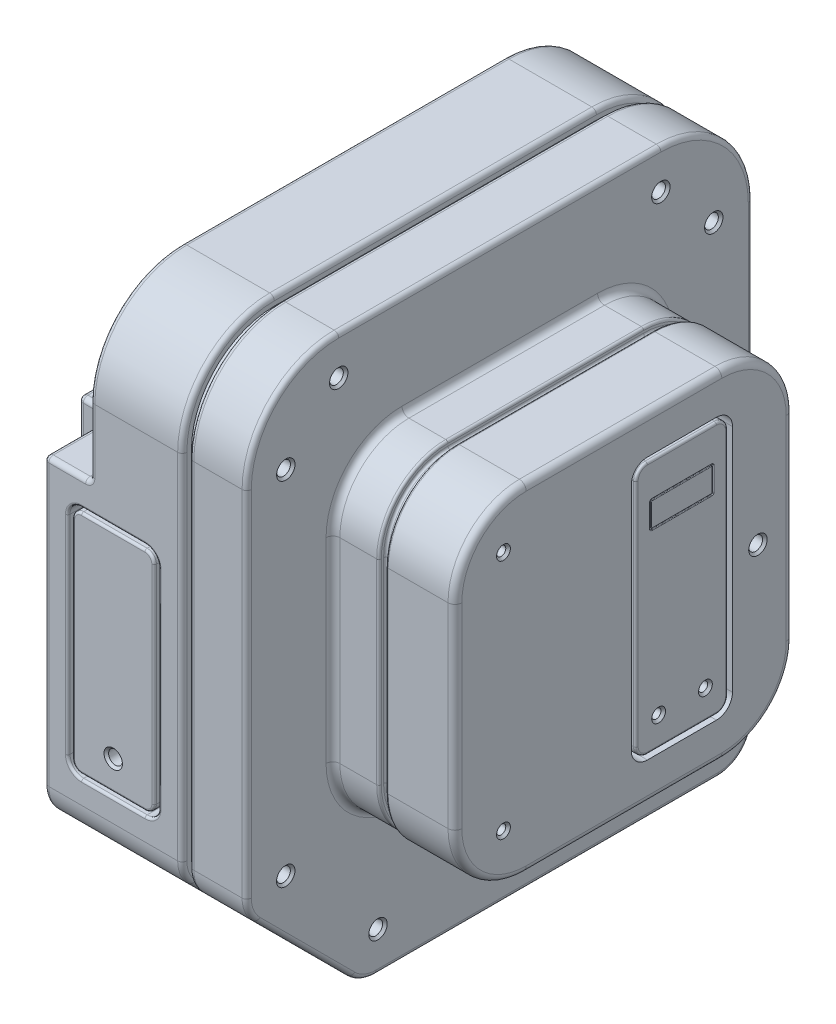
SolidWorks part; units mm, degrees
material "moto_black"
ref_plane "Front Plane" through (0, 0, 0) normal (0, 0, 1) x (1, 0, 0)
ref_plane "Top Plane" through (0, 0, 0) normal (0, 1, 0) x (1, 0, 0)
ref_plane "Right Plane" through (0, 0, 0) normal (1, 0, 0) x (0, 0, -1)
sketch "Sketch1" plane through (0, 0, 0) normal (1, 0, 0) x (0, 0, -1)
  line L0 (-105.6066, -79.3934) -> (-64.3934, -120.6066)
  line L1 (-70, 125) -> (70, 125)
  line L2 (-110, 85) -> (-110, -68.7868)
  line L3 (-53.7868, -125) -> (95, -125)
  line L4 (110, 85) -> (110, -110)
  line L5 (-110, 125) -> (110, -125) construction
  line L6 (-110, -125) -> (110, 125) construction
  arc A0 (70, 125) -> (110, 85) centre (70, 85) cw
  arc A1 (-70, 125) -> (-110, 85) centre (-70, 85) ccw
  arc A2 (95, -125) -> (110, -110) centre (95, -110) ccw
  arc A3 (-105.6066, -79.3934) -> (-110, -68.7868) centre (-95, -68.7868) cw
  arc A4 (-64.3934, -120.6066) -> (-53.7868, -125) centre (-53.7868, -110) ccw
  point P0 (0, 0)
  point P20 (-110, -75)
  point P23 (-60, -125)
  dimension "D3" = 40
  dimension "D4" = 15
  dimension "D5" = 15
  dimension "D1" = 250
  dimension "D2" = 220
extrude "Boss-Extrude1" add sketch "Sketch1" along normal blind 25
sketch "Sketch2" plane through (0, 0, 0) normal (-1, 0, 0) x (0, 0, 1)
  line L10 (-106, 85) -> (-106, -110)
  line L11 (-95, -121) -> (53.7868, -121)
  line L12 (61.565, -117.7782) -> (102.7782, -76.565)
  line L13 (106, -68.7868) -> (106, 85)
  line L14 (70, 121) -> (-70, 121)
  line L15 (-106, 85) -> (-106, -110)
  line L16 (-95, -121) -> (53.7868, -121)
  line L17 (61.565, -117.7782) -> (102.7782, -76.565)
  line L18 (106, -68.7868) -> (106, 85)
  line L19 (70, 121) -> (-70, 121)
  arc A10 (-70, 121) -> (-106, 85) centre (-70, 85) ccw
  arc A11 (-106, -110) -> (-95, -121) centre (-95, -110) ccw
  arc A12 (53.7868, -121) -> (61.565, -117.7782) centre (53.7868, -110) ccw
  arc A13 (102.7782, -76.565) -> (106, -68.7868) centre (95, -68.7868) ccw
  arc A14 (106, 85) -> (70, 121) centre (70, 85) ccw
  arc A15 (-70, 121) -> (-106, 85) centre (-70, 85) ccw
  arc A16 (-106, -110) -> (-95, -121) centre (-95, -110) ccw
  arc A17 (53.7868, -121) -> (61.565, -117.7782) centre (53.7868, -110) ccw
  arc A18 (102.7782, -76.565) -> (106, -68.7868) centre (95, -68.7868) ccw
  arc A19 (106, 85) -> (70, 121) centre (70, 85) ccw
  dimension "D1" = 4
extrude "Boss-Extrude2" add sketch "Sketch2" along normal blind 3
sketch "Sketch3" plane through (-3, 0, 0) normal (-1, 0, 0) x (0, 0, 1)
  line L10 (-110, 85) -> (-110, -110)
  line L11 (-95, -125) -> (53.7868, -125)
  line L12 (64.3934, -120.6066) -> (105.6066, -79.3934)
  line L13 (110, -68.7868) -> (110, 85)
  line L14 (70, 125) -> (-70, 125)
  line L15 (-110, 85) -> (-110, -110)
  line L16 (-95, -125) -> (53.7868, -125)
  line L17 (64.3934, -120.6066) -> (105.6066, -79.3934)
  line L18 (110, -68.7868) -> (110, 85)
  line L19 (70, 125) -> (-70, 125)
  arc A10 (-70, 125) -> (-110, 85) centre (-70, 85) ccw
  arc A11 (-110, -110) -> (-95, -125) centre (-95, -110) ccw
  arc A12 (53.7868, -125) -> (64.3934, -120.6066) centre (53.7868, -110) ccw
  arc A13 (105.6066, -79.3934) -> (110, -68.7868) centre (95, -68.7868) ccw
  arc A14 (110, 85) -> (70, 125) centre (70, 85) ccw
  arc A15 (-70, 125) -> (-110, 85) centre (-70, 85) ccw
  arc A16 (-110, -110) -> (-95, -125) centre (-95, -110) ccw
  arc A17 (53.7868, -125) -> (64.3934, -120.6066) centre (53.7868, -110) ccw
  arc A18 (105.6066, -79.3934) -> (110, -68.7868) centre (95, -68.7868) ccw
  arc A19 (110, 85) -> (70, 125) centre (70, 85) ccw
  dimension "D1" = 4
extrude "Boss-Extrude3" add sketch "Sketch3" along normal blind 40
sketch "Sketch4" plane through (25, 0, 0) normal (1, 0, 0) x (0, 0, -1)
  line L0 (-110, 8.1066) -> (110, 8.1066)
  line L1 (-110, 85) -> (-110, -68.7868) construction
  line L2 (110, -110) -> (110, 85) construction
  line L3 (0, 125) -> (0, 8.1066)
  line L4 (70, 125) -> (-70, 125) construction
  line L6 (-42.5, -64.3934) -> (42.5, -64.3934)
  line L7 (-72.5, -34.3934) -> (-72.5, 50.6066)
  line L8 (-42.5, 80.6066) -> (42.5, 80.6066)
  line L9 (72.5, -34.3934) -> (72.5, 50.6066)
  line L10 (-72.5, -64.3934) -> (72.5, 80.6066) construction
  line L11 (-72.5, 80.6066) -> (72.5, -64.3934) construction
  arc A0 (42.5, 80.6066) -> (72.5, 50.6066) centre (42.5, 50.6066) cw
  arc A1 (42.5, -64.3934) -> (72.5, -34.3934) centre (42.5, -34.3934) ccw
  arc A2 (-42.5, -64.3934) -> (-72.5, -34.3934) centre (-42.5, -34.3934) cw
  arc A3 (-72.5, 50.6066) -> (-42.5, 80.6066) centre (-42.5, 50.6066) cw
  dimension "D3" = 30
  dimension "D1" = 145
  dimension "D2" = 145
extrude "Boss-Extrude5" add sketch "Sketch4" along normal blind 20 contours A0 L8 L3 L0 L9 | A3 L7 L0 L3 L8 | A2 L6 A1 L9 L0 L7 region at (25, 43.2294, 35.1228) region at (25, -27.0162, 0) region at (25, 43.2294, -35.1228)
sketch "Sketch7" plane through (45, 0, 0) normal (1, 0, 0) x (0, 0, -1)
  line L8 (42.5, 77.6066) -> (-42.5, 77.6066)
  line L9 (-69.5, 50.6066) -> (-69.5, -34.3934)
  line L10 (-42.5, -61.3934) -> (42.5, -61.3934)
  line L11 (69.5, -34.3934) -> (69.5, 50.6066)
  line L12 (42.5, 77.6066) -> (-42.5, 77.6066)
  line L13 (-69.5, 50.6066) -> (-69.5, -34.3934)
  line L14 (-42.5, -61.3934) -> (42.5, -61.3934)
  line L15 (69.5, -34.3934) -> (69.5, 50.6066)
  arc A8 (69.5, 50.6066) -> (42.5, 77.6066) centre (42.5, 50.6066) ccw
  arc A9 (-42.5, 77.6066) -> (-69.5, 50.6066) centre (-42.5, 50.6066) ccw
  arc A10 (-69.5, -34.3934) -> (-42.5, -61.3934) centre (-42.5, -34.3934) ccw
  arc A11 (42.5, -61.3934) -> (69.5, -34.3934) centre (42.5, -34.3934) ccw
  arc A12 (69.5, 50.6066) -> (42.5, 77.6066) centre (42.5, 50.6066) ccw
  arc A13 (-42.5, 77.6066) -> (-69.5, 50.6066) centre (-42.5, 50.6066) ccw
  arc A14 (-69.5, -34.3934) -> (-42.5, -61.3934) centre (-42.5, -34.3934) ccw
  arc A15 (42.5, -61.3934) -> (69.5, -34.3934) centre (42.5, -34.3934) ccw
  dimension "D1" = 3
extrude "Boss-Extrude6" add sketch "Sketch7" along normal blind 4
sketch "Sketch8" plane through (49, 0, 0) normal (1, 0, 0) x (0, 0, -1)
  line L8 (42.5, 81.6066) -> (-42.5, 81.6066)
  line L9 (-73.5, 50.6066) -> (-73.5, -34.3934)
  line L10 (-42.5, -65.3934) -> (42.5, -65.3934)
  line L11 (73.5, -34.3934) -> (73.5, 50.6066)
  line L12 (42.5, 81.6066) -> (-42.5, 81.6066)
  line L13 (-73.5, 50.6066) -> (-73.5, -34.3934)
  line L14 (-42.5, -65.3934) -> (42.5, -65.3934)
  line L15 (73.5, -34.3934) -> (73.5, 50.6066)
  arc A8 (73.5, 50.6066) -> (42.5, 81.6066) centre (42.5, 50.6066) ccw
  arc A9 (-42.5, 81.6066) -> (-73.5, 50.6066) centre (-42.5, 50.6066) ccw
  arc A10 (-73.5, -34.3934) -> (-42.5, -65.3934) centre (-42.5, -34.3934) ccw
  arc A11 (42.5, -65.3934) -> (73.5, -34.3934) centre (42.5, -34.3934) ccw
  arc A12 (73.5, 50.6066) -> (42.5, 81.6066) centre (42.5, 50.6066) ccw
  arc A13 (-42.5, 81.6066) -> (-73.5, 50.6066) centre (-42.5, 50.6066) ccw
  arc A14 (-73.5, -34.3934) -> (-42.5, -65.3934) centre (-42.5, -34.3934) ccw
  arc A15 (42.5, -65.3934) -> (73.5, -34.3934) centre (42.5, -34.3934) ccw
  dimension "D1" = 4
extrude "Boss-Extrude7" add sketch "Sketch8" along normal blind 30
sketch "Sketch9" plane through (79, 0, 0) normal (1, 0, 0) x (0, 0, -1)
  line L0 (-73.5, 8.1066) -> (73.5, 8.1066)
  line L1 (-73.5, 50.6066) -> (-73.5, -34.3934) construction
  line L2 (73.5, -34.3934) -> (73.5, 50.6066) construction
  line L3 (10.149, 65.1066) -> (40.149, 65.1066)
  line L4 (10.149, -46.8934) -> (40.149, -46.8934)
  line L5 (5.149, -41.8934) -> (5.149, 58.1066)
  line L6 (10.149, 63.1066) -> (40.149, 63.1066)
  line L7 (45.149, -41.8934) -> (45.149, 58.1066)
  line L8 (5.149, -46.8934) -> (45.149, 63.1066) construction
  line L9 (5.149, 63.1066) -> (45.149, -46.8934) construction
  line L10 (47.149, -41.8934) -> (47.149, 58.1066)
  line L11 (10.149, -48.8934) -> (40.149, -48.8934)
  line L12 (3.149, -41.8934) -> (3.149, 58.1066)
  line L13 (7.149, -41.8934) -> (7.149, 58.1066)
  line L14 (12.2764, 48.3553) -> (38.0216, 48.3553)
  line L15 (11.2764, 47.3553) -> (11.2764, 37.7014)
  line L16 (12.2764, 36.7014) -> (38.0216, 36.7014)
  line L17 (39.0216, 47.3553) -> (39.0216, 37.7014)
  line L18 (11.2764, 48.3553) -> (39.0216, 36.7014) construction
  line L19 (11.2764, 36.7014) -> (39.0216, 48.3553) construction
  line L20 (10.149, 61.1066) -> (40.149, 61.1066)
  line L21 (43.149, -41.8934) -> (43.149, 58.1066)
  line L22 (10.149, -44.8934) -> (40.149, -44.8934)
  line L23 (12.2764, 47.8553) -> (38.0216, 47.8553)
  line L24 (38.5216, 47.3553) -> (38.5216, 37.7014)
  line L25 (12.2764, 37.2014) -> (38.0216, 37.2014)
  line L26 (11.7764, 47.3553) -> (11.7764, 37.7014)
  arc A0 (10.149, -46.8934) -> (5.149, -41.8934) centre (10.149, -41.8934) cw
  arc A1 (40.149, -46.8934) -> (45.149, -41.8934) centre (40.149, -41.8934) ccw
  arc A2 (40.149, 63.1066) -> (45.149, 58.1066) centre (40.149, 58.1066) cw
  arc A3 (5.149, 58.1066) -> (10.149, 63.1066) centre (10.149, 58.1066) cw
  arc A4 (40.149, 65.1066) -> (47.149, 58.1066) centre (40.149, 58.1066) cw
  arc A5 (40.149, -48.8934) -> (47.149, -41.8934) centre (40.149, -41.8934) ccw
  arc A6 (10.149, -48.8934) -> (3.149, -41.8934) centre (10.149, -41.8934) cw
  arc A7 (3.149, 58.1066) -> (10.149, 65.1066) centre (10.149, 58.1066) cw
  arc A8 (38.0216, 48.3553) -> (39.0216, 47.3553) centre (38.0216, 47.3553) cw
  arc A9 (38.0216, 36.7014) -> (39.0216, 37.7014) centre (38.0216, 37.7014) ccw
  arc A10 (11.2764, 37.7014) -> (12.2764, 36.7014) centre (12.2764, 37.7014) ccw
  arc A11 (12.2764, 48.3553) -> (11.2764, 47.3553) centre (12.2764, 47.3553) ccw
  arc A12 (7.149, 58.1066) -> (10.149, 61.1066) centre (10.149, 58.1066) cw
  arc A13 (40.149, 61.1066) -> (43.149, 58.1066) centre (40.149, 58.1066) cw
  arc A14 (40.149, -44.8934) -> (43.149, -41.8934) centre (40.149, -41.8934) ccw
  arc A15 (10.149, -44.8934) -> (7.149, -41.8934) centre (10.149, -41.8934) cw
  arc A16 (38.0216, 47.8553) -> (38.5216, 47.3553) centre (38.0216, 47.3553) cw
  arc A17 (38.0216, 37.2014) -> (38.5216, 37.7014) centre (38.0216, 37.7014) ccw
  arc A18 (11.7764, 37.7014) -> (12.2764, 37.2014) centre (12.2764, 37.7014) ccw
  arc A19 (12.2764, 47.8553) -> (11.7764, 47.3553) centre (12.2764, 47.3553) ccw
  point P6 (25.149, 8.1066)
  point P37 (25.149, 42.5284)
  dimension "D3" = 5
  dimension "D5" = 1
  dimension "D1" = 40
  dimension "D2" = 110
  dimension "D4" = 2
  dimension "D6" = 2
  dimension "D7" = 0.5
extrude "Cut-Extrude1" cut sketch "Sketch9" against normal blind 15 contours A7 L12 L0 L5 A3 L6 A2 L7 L10 A4 L3 | A6 L11 A5 L10 L0 L7 A1 L4 A0 L5 L12 region at (79, 33.1066, -3.8691) region at (79, 7.3865, -4.149)
extrude "Cut-Extrude2" cut sketch "Sketch9<5>" against normal blind 4 contours L14 A11 L15 A10 L16 A9 L17 A8 A19 L23 A16 L24 A17 L25 A18 L26 region at (79, 48.0544, -25.149)
sketch "Sketch9<5>" plane through (79, 0, 0) normal (1, 0, 0) x (0, 0, -1) same geometry as "Sketch9"
sketch "Sketch10" plane through (-43, 0, 0) normal (-1, 0, 0) x (0, 0, 1)
  line L10 (-110, 55) -> (110, 55)
  line L15 (-110, 85) -> (-110, -110)
  line L16 (-95, -125) -> (53.7868, -125)
  line L17 (64.3934, -120.6066) -> (105.6066, -79.3934)
  line L18 (110, -68.7868) -> (110, 85)
  line L19 (70, 125) -> (-70, 125)
  line L20 (-110, 85) -> (-110, -110)
  line L21 (-95, -125) -> (53.7868, -125)
  line L22 (64.3934, -120.6066) -> (105.6066, -79.3934)
  line L23 (110, -68.7868) -> (110, 85)
  line L24 (70, 125) -> (-70, 125)
  arc A15 (-70, 125) -> (-110, 85) centre (-70, 85) ccw
  arc A16 (-110, -110) -> (-95, -125) centre (-95, -110) ccw
  arc A17 (53.7868, -125) -> (64.3934, -120.6066) centre (53.7868, -110) ccw
  arc A18 (105.6066, -79.3934) -> (110, -68.7868) centre (95, -68.7868) ccw
  arc A19 (110, 85) -> (70, 125) centre (70, 85) ccw
  arc A20 (-70, 125) -> (-110, 85) centre (-70, 85) ccw
  arc A21 (-110, -110) -> (-95, -125) centre (-95, -110) ccw
  arc A22 (53.7868, -125) -> (64.3934, -120.6066) centre (53.7868, -110) ccw
  arc A23 (105.6066, -79.3934) -> (110, -68.7868) centre (95, -68.7868) ccw
  arc A24 (110, 85) -> (70, 125) centre (70, 85) ccw
  dimension "D2" = 70
  dimension "D1" = 0
extrude "Boss-Extrude8" add sketch "Sketch10" along normal blind 20 contours L10 L20 A21 L21 A22 L22 A23 L23 region at (-43, -32.4806, -2.9336)
sketch "Sketch11" plane through (-63, 0, 0) normal (-1, 0, 0) x (0, 0, 1)
  line L0 (-110, 55) -> (110, 55) construction
  line L1 (-80, 55) -> (80, 55)
  line L2 (-80, 55) -> (-80, -65)
  line L3 (-50, -95) -> (50, -95)
  line L4 (80, 55) -> (80, -65)
  line L5 (110, -68.7868) -> (110, 55) construction
  line L6 (-110, 55) -> (-110, -110) construction
  line L7 (-95, -125) -> (53.7868, -125) construction
  arc A0 (50, -95) -> (80, -65) centre (50, -65) ccw
  arc A1 (-80, -65) -> (-50, -95) centre (-50, -65) ccw
  dimension "D4" = 30
  dimension "D5" = 30
  dimension "D1" = 30
  dimension "D2" = 30
  dimension "D3" = 30
extrude "Boss-Extrude9" add sketch "Sketch11" along normal blind 15
sketch "Sketch13" plane through (-78, 0, 0) normal (-1, 0, 0) x (0, 0, 1)
  line L0 (0, 55) -> (0, -95)
  line L1 (-110, 55) -> (110, 55) construction
  line L2 (-50, -95) -> (50, -95) construction
  line L3 (0, -20) -> (29.0398, -20)
  line L5 (7.0711, -12.9289) -> (-49.4975, 43.6396)
  line L6 (-7.0711, -27.0711) -> (-63.6396, 29.4975)
  line L7 (-56.5685, 43.6396) -> (-63.6396, 36.5685)
  line L8 (7.0711, -12.9289) -> (-7.0711, -27.0711)
  circle A0 centre (0, -20) radius 62.0906
  circle A1 centre (0, -20) radius 47.0906
  arc A2 (-63.6396, 29.4975) -> (-63.6396, 36.5685) centre (-60.1041, 33.033) cw
  arc A3 (-49.4975, 43.6396) -> (-56.5685, 43.6396) centre (-53.033, 40.1041) ccw
  dimension "D2" = 5
  dimension "D1" = 15
extrude "Boss-Extrude10" add sketch "Sketch13" along normal blind 25 contours A1 L0 A0 | A1 L0 A0 L5 | A1 L5 A0 L6 | A1 L6 A0 L0 | L5 A3 L7 A2 L6 A0 region at (-78, 22.923, 42.923) region at (-78, 31.7668, -16.0891) region at (-78, 31.7327, -51.7327) region at (-78, 18.3791, -38.3791) region at (-78, -47.7875, -54.2219)
sketch "Sketch14" plane through (-78, 0, 0) normal (-1, 0, 0) x (0, 0, 1)
  circle A0 centre (0, -20.0167) radius 36.8224
extrude "Boss-Extrude11" add sketch "Sketch14" along normal blind 75
fillet "Fillet1" radius 2 30 edges at (-3, 113.2843, -98.2843) (-3, 125, 0) (-3, 113.2843, 98.2843) (-3, 8.1066, 110) (-3, -74.527, 108.8582) (-3, -100, 85) (-3, -123.8582, 59.527) (-3, -125, -20.6066) (-3, -120.6066, -105.6066) (-3, -12.5, -110) (25, -120.6066, -105.6066) (25, -125, -20.6066) (25, -123.8582, 59.527) (25, -100, 85) (25, -74.527, 108.8582) (25, 8.1066, 110) (25, 113.2843, 98.2843) (25, 125, 0) (25, 113.2843, -98.2843) (0, -120.6066, -105.6066) (0, -125, -20.6066) (0, -123.8582, 59.527) (0, -100, 85) (0, -74.527, 108.8582) (0, 8.1066, 110) (0, 113.2843, 98.2843) (0, 125, 0) (0, 113.2843, -98.2843) (25, -12.5, -110) (0, -12.5, -110)
fillet "Fillet2" radius 1 32 edges at (49, 8.1066, -69.5) (49, -53.4853, -61.5919) (49, -61.3934, 0) (49, -53.4853, 61.5919) (49, 8.1066, 69.5) (49, 69.6985, 61.5919) (49, 77.6066, 0) (45, 8.1066, -69.5) (45, -53.4853, -61.5919) (45, -61.3934, 0) (45, -53.4853, 61.5919) (45, 8.1066, 69.5) (45, 69.6985, 61.5919) (45, 77.6066, 0) (49, 8.1066, -73.5) (49, -56.3137, -64.4203) (49, -65.3934, 0) (49, -56.3137, 64.4203) (49, 8.1066, 73.5) (49, 72.5269, 64.4203) (49, 81.6066, 0) (45, 80.6066, 0) (45, 71.8198, 63.7132) (45, 8.1066, 72.5) (45, -55.6066, 63.7132) (45, -64.3934, 0) (45, -55.6066, -63.7132) (45, 8.1066, -72.5) (49, 69.6985, -61.5919) (45, 69.6985, -61.5919) (49, 72.5269, -64.4203) (45, 71.8198, -63.7132)
fillet "Fillet3" radius 3 8 edges at (25, 80.6066, 0) (25, 71.8198, 63.7132) (25, 8.1066, 72.5) (25, -55.6066, 63.7132) (25, -64.3934, 0) (25, -55.6066, -63.7132) (25, 8.1066, -72.5) (25, 71.8198, -63.7132)
fillet "Fillet4" radius 3 8 edges at (79, 72.5269, -64.4203) (79, 8.1066, -73.5) (79, -56.3137, -64.4203) (79, -65.3934, 0) (79, -56.3137, 64.4203) (79, 8.1066, 73.5) (79, 72.5269, 64.4203) (79, 81.6066, 0)
fillet "Fillet6" radius 1 8 edges at (79, 63.1066, -25.149) (79, 61.6421, -6.6135) (79, 8.1066, -5.149) (79, -45.4289, -6.6135) (79, -46.8934, -25.149) (79, -45.4289, -43.6846) (79, 8.1066, -45.149) (79, 61.6421, -43.6846)
fillet "Fillet7" radius 0.25 16 edges at (79, 48.0624, -38.7287) (79, 48.3553, -25.149) (79, 48.0624, -11.5693) (79, 42.5284, -11.2764) (79, 36.9943, -11.5693) (79, 36.7014, -25.149) (79, 36.9943, -38.7287) (79, 47.7089, -38.3752) (79, 42.5284, -38.5216) (79, 37.3479, -38.3752) (79, 37.2014, -25.149) (79, 37.3479, -11.9229) (79, 42.5284, -11.7764) (79, 47.7089, -11.9229) (79, 47.8553, -25.149) (79, 42.5284, -39.0216)
fillet "Fillet8" radius 2 1 edges at (-43, 55, 0)
fillet "Fillet9" radius 2 26 edges at (-70.5, 55, 80) (-70.5, 55, -80) (-54, 55, 110) (-43.5858, 55.5858, 110) (-54, 55, -110) (-43.5858, 55.5858, -110) (-63, -86.2132, -71.2132) (-63, -95, 0) (-63, -86.2132, 71.2132) (-63, -5, 80) (-63, 55, 95) (-63, -6.8934, 110) (-63, -74.527, 108.8582) (-63, -100, 85) (-63, -123.8582, 59.527) (-63, -125, -20.6066) (-63, -120.6066, -105.6066) (-63, -27.5, -110) (-63, 55, -95) (-63, -5, -80) (-43, 113.2843, -98.2843) (-43, 125, 0) (-43, 113.2843, 98.2843) (-43, 71, 110) (-43, 71, -110) (-78, 55, 0)
fillet "Fillet10" radius 2 20 edges at (-77.4142, 54.4142, -79.4142) (-77.4142, 54.4142, 79.4142) (-103, -20, 47.0906) (-103, 22.879, -57.0211) (-103, 33.033, -65.1041) (-103, 40.1041, -60.1041) (-103, 45.1041, -53.033) (-103, 37.0211, -42.879) (-103, -63.9047, 43.9047) (-78, -86.2132, 71.2132) (-78, -95, 0) (-78, -86.2132, -71.2132) (-78, -6, -80) (-78, -6, 80) (-78, 37.0211, -42.879) (-78, 45.1041, -53.033) (-78, 40.1041, -60.1041) (-78, 33.033, -65.1041) (-78, 22.879, -57.0211) (-78, -63.9047, 43.9047)
sketch "Sketch17" plane through (-153, 0, 0) normal (-1, 0, 0) x (0, 0, 1)
  circle A2 centre (0, -20.0167) radius 36.8224
  circle A3 centre (0, -20.0167) radius 36.8224
  dimension "D1" = 0
extrude "Cut-Extrude3" cut sketch "Sketch17" against normal blind 36
sketch "Sketch18" plane through (79, 0, 0) normal (1, 0, 0) x (0, 0, -1)
  line L0 (70.5, 50.6066) -> (-70.5, 50.6066)
  line L1 (25.2024, -34.3934) -> (25.2024, -25.0283)
  line L2 (-42.5, 78.6066) -> (-42.5, -62.3934)
  line L6 (0, 78.6066) -> (0, -62.3934)
  line L8 (70.5, -34.3934) -> (70.5, 50.6066)
  line L9 (42.5, 78.6066) -> (-42.5, 78.6066)
  line L10 (-70.5, 50.6066) -> (-70.5, -34.3934)
  line L11 (-42.5, -62.3934) -> (42.5, -62.3934)
  line L12 (70.5, -34.3934) -> (70.5, 50.6066)
  line L13 (42.5, 78.6066) -> (-42.5, 78.6066)
  line L14 (-70.5, 50.6066) -> (-70.5, -34.3934)
  line L15 (-42.5, -62.3934) -> (42.5, -62.3934)
  line L18 (44.1202, -34.3934) -> (6.2845, -34.3934)
  circle A0 centre (-52.3995, 60.5061) radius 2
  circle A1 centre (-52.3995, -44.2929) radius 2
  circle A2 centre (58.1938, 8.1066) radius 3
  circle A3 centre (15.0333, -34.3934) radius 2
  circle A4 centre (35.3714, -34.3934) radius 2
  arc A8 (70.5, 50.6066) -> (42.5, 78.6066) centre (42.5, 50.6066) ccw
  arc A9 (-42.5, 78.6066) -> (-70.5, 50.6066) centre (-42.5, 50.6066) ccw
  arc A10 (-70.5, -34.3934) -> (-42.5, -62.3934) centre (-42.5, -34.3934) ccw
  arc A11 (42.5, -62.3934) -> (70.5, -34.3934) centre (42.5, -34.3934) ccw
  arc A12 (70.5, 50.6066) -> (42.5, 78.6066) centre (42.5, 50.6066) ccw
  arc A13 (-42.5, 78.6066) -> (-70.5, 50.6066) centre (-42.5, 50.6066) ccw
  arc A14 (-70.5, -34.3934) -> (-42.5, -62.3934) centre (-42.5, -34.3934) ccw
  arc A15 (42.5, -62.3934) -> (70.5, -34.3934) centre (42.5, -34.3934) ccw
  dimension "D2" = 4
  dimension "D3" = 4
  dimension "D4" = 6
  dimension "D5" = 4
  dimension "D1" = 0
sketch "Sketch19" plane through (25, 0, 0) normal (1, 0, 0) x (0, 0, -1)
  line L0 (0, 123) -> (0, 103.1719)
  line L5 (-93.0243, -67.9341) -> (-52.9341, -108.0243)
  line L10 (-53.7868, -123) -> (95, -123)
  line L11 (108, -110) -> (108, 85)
  line L12 (70, 123) -> (-70, 123)
  line L13 (-108, 85) -> (-108, -68.7868)
  line L14 (-104.1924, -77.9792) -> (-62.9792, -119.1924)
  line L15 (-53.7868, -123) -> (95, -123)
  line L16 (108, -110) -> (108, 85)
  line L17 (70, 123) -> (-70, 123)
  line L18 (-108, 85) -> (-108, -68.7868)
  line L19 (-104.1924, -77.9792) -> (-62.9792, -119.1924)
  circle A0 centre (-93.0243, -67.9341) radius 3
  circle A1 centre (-70, 108) radius 3
  circle A2 centre (-93, 85) radius 3
  circle A3 centre (70, 108) radius 3
  circle A4 centre (93, 85) radius 3
  arc A5 (-70, 108) -> (-93, 85) centre (-70, 85) ccw
  arc A6 (93, 85) -> (70, 108) centre (70, 85) ccw
  arc A7 (-93.0243, -67.9341) -> (-93.0243, -67.9341) centre (-93.0243, -67.9341) ccw
  arc A8 (-52.9341, -108.0243) -> (-52.9341, -108.0243) centre (-52.9341, -108.0243) ccw
  arc A9 (95, -112) -> (97, -110) centre (95, -110) ccw
  arc A10 (95, -123) -> (108, -110) centre (95, -110) ccw
  arc A11 (108, 85) -> (70, 123) centre (70, 85) ccw
  arc A12 (-70, 123) -> (-108, 85) centre (-70, 85) ccw
  arc A13 (-108, -68.7868) -> (-104.1924, -77.9792) centre (-95, -68.7868) ccw
  arc A14 (-62.9792, -119.1924) -> (-53.7868, -123) centre (-53.7868, -110) ccw
  arc A15 (95, -123) -> (108, -110) centre (95, -110) ccw
  arc A16 (108, 85) -> (70, 123) centre (70, 85) ccw
  arc A17 (-70, 123) -> (-108, 85) centre (-70, 85) ccw
  arc A18 (-108, -68.7868) -> (-104.1924, -77.9792) centre (-95, -68.7868) ccw
  arc A19 (-62.9792, -119.1924) -> (-53.7868, -123) centre (-53.7868, -110) ccw
  circle A20 centre (95, -110) radius 3
  circle A21 centre (-52.9341, -108.0243) radius 3
  dimension "D6" = 6
  dimension "D7" = 6
  dimension "D8" = 6
  dimension "D9" = 6
  dimension "D10" = 6
  dimension "D11" = 6
  dimension "D12" = 6
  dimension "D1" = 0
  dimension "D2" = 15
  dimension "D3" = 15
  dimension "D4" = 15
  dimension "D5" = 11
sketch "Sketch20" plane through (-43, 0, 0) normal (-1, 0, 0) x (0, 0, 1)
  line L4 (-96.8701, 111.8701) -> (-70, 85)
  line L5 (96.8701, 111.8701) -> (70, 85)
  line L6 (-83.435, 98.435) -> (83.435, 98.435)
  line L7 (0, 98.435) -> (0, 123)
  line L8 (-108, 57) -> (108, 57)
  line L9 (108, 57) -> (108, 85)
  line L10 (70, 123) -> (-70, 123)
  line L11 (-108, 85) -> (-108, 57)
  line L12 (-108, 57) -> (108, 57)
  line L13 (108, 57) -> (108, 85)
  line L14 (70, 123) -> (-70, 123)
  line L15 (-108, 85) -> (-108, 57)
  line L18 (81, 65.1068) -> (81, 74.8231)
  circle A2 centre (81, 65.1068) radius 3
  circle A3 centre (-83.435, 98.435) radius 3
  arc A4 (108, 85) -> (70, 123) centre (70, 85) ccw
  arc A5 (-70, 123) -> (-108, 85) centre (-70, 85) ccw
  arc A6 (108, 85) -> (70, 123) centre (70, 85) ccw
  arc A7 (-70, 123) -> (-108, 85) centre (-70, 85) ccw
  circle A8 centre (0, 111.8701) radius 3
  circle A9 centre (83.435, 98.435) radius 3
  dimension "D2" = 6
  dimension "D3" = 6
  dimension "D4" = 6
  dimension "D5" = 6
  dimension "D1" = 0
sketch "Sketch21" plane through (-63, 0, 0) normal (-1, 0, 0) x (0, 0, 1)
  line L18 (50, -97) -> (-50, -97)
  line L19 (-82, -65) -> (-82, 53)
  line L20 (-82, 53) -> (-108, 53)
  line L21 (-108, 53) -> (-108, -110)
  line L22 (-95, -123) -> (53.7868, -123)
  line L23 (62.9792, -119.1924) -> (104.1924, -77.9792)
  line L24 (108, -68.7868) -> (108, 53)
  line L25 (108, 53) -> (82, 53)
  line L26 (82, 53) -> (82, -65)
  line L27 (50, -97) -> (-50, -97)
  line L28 (-82, -65) -> (-82, 53)
  line L29 (-82, 53) -> (-108, 53)
  line L30 (-108, 53) -> (-108, -110)
  line L31 (-95, -123) -> (53.7868, -123)
  line L32 (62.9792, -119.1924) -> (104.1924, -77.9792)
  line L33 (108, -68.7868) -> (108, 53)
  line L34 (108, 53) -> (82, 53)
  line L35 (82, 53) -> (82, -65)
  circle A5 centre (-95, -110) radius 3
  circle A6 centre (53.7868, -110) radius 2
  circle A7 centre (95, -68.7868) radius 2
  circle A8 centre (-95, 34.752) radius 3
  circle A9 centre (-95, 34.752) radius 3
  arc A10 (-82, -65) -> (-50, -97) centre (-50, -65) ccw
  arc A11 (-108, -110) -> (-95, -123) centre (-95, -110) ccw
  arc A12 (53.7868, -123) -> (62.9792, -119.1924) centre (53.7868, -110) ccw
  arc A13 (104.1924, -77.9792) -> (108, -68.7868) centre (95, -68.7868) ccw
  arc A14 (50, -97) -> (82, -65) centre (50, -65) ccw
  arc A15 (-82, -65) -> (-50, -97) centre (-50, -65) ccw
  arc A16 (-108, -110) -> (-95, -123) centre (-95, -110) ccw
  arc A17 (53.7868, -123) -> (62.9792, -119.1924) centre (53.7868, -110) ccw
  arc A18 (104.1924, -77.9792) -> (108, -68.7868) centre (95, -68.7868) ccw
  arc A19 (50, -97) -> (82, -65) centre (50, -65) ccw
  circle A20 centre (-95, -110) radius 3
  circle A21 centre (53.7868, -110) radius 2
  circle A22 centre (95, -68.7868) radius 2
  dimension "D2" = 6
  dimension "D3" = 4
  dimension "D4" = 4
  dimension "D5" = 6
  dimension "D1" = 0
  dimension "D6" = 0
extrude "Cut-Extrude4" cut sketch "Sketch18" against normal blind 10 contours A0 | A2 | A1 | A4 L18 | A4 L18 | L18 A3 | L18 A3 region at (79, -35.2422, -15.0333) region at (79, -33.5446, -15.0333) region at (79, -33.5446, -35.3714) region at (79, -35.2422, -35.3714) region at (79, 60.5061, 52.3995) region at (79, -44.2929, 52.3995) region at (79, 8.1066, -58.1938)
extrude "Cut-Extrude5" cut sketch "Sketch19" against normal blind 10 contours A1 | A2 | A3 | A4 | A20 | A21 | A0 region at (25, -105.331, 51.8185) region at (25, -66.8185, 95.7175) region at (25, 105.0864, 69.9049) region at (25, 86.993, 90.8725) region at (25, 107.9049, -72.9136) region at (25, 87.1275, -94.993) region at (25, -110, -95)
extrude "Cut-Extrude6" cut sketch "Sketch20" against normal blind 10 contours L4 A3 | L6 A3 L4 | L4 A3 L6 | L7 A8 | L7 A8 | L5 A9 | L5 A9 L6 | L6 A9 L5 | A2 region at (-43, 99.8841, -82.8348) region at (-43, 97.5347, -84.3353) region at (-43, 97.6892, -81.6344) region at (-43, 111.8701, 1.2732) region at (-43, 111.8701, -1.2732) region at (-43, 99.8841, 82.8348) region at (-43, 97.6892, 81.6344) region at (-43, 97.5347, 84.3353) region at (-43, 63.0454, 78.9387)
extrude "Cut-Extrude7" cut sketch "Sketch21" against normal blind 10 contours A8 | A5 | A6 | A7 region at (-63, -110, -95) region at (-63, -110, 53.7868) region at (-63, -68.7868, 95) region at (-63, 34.752, -95)
chamfer "Chamfer1" distance 1 angle 45 4 edges at (79, 60.5061, 50.3995) (79, -44.2929, 50.3995) (79, -34.3934, -37.3714) (79, -34.3934, -17.0333)
chamfer "Chamfer2" distance 1 angle 45 1 edges at (79, 8.1066, -61.1938)
chamfer "Chamfer3" distance 1 angle 45 7 edges at (25, -67.9341, 90.0243) (25, -108.0243, 49.9341) (25, -110, -98) (25, 85, -96) (25, 108, -73) (25, 108, 67) (25, 85, 90)
chamfer "Chamfer4" distance 1 angle 45 9 edges at (-63, -68.7868, 97) (-53, -68.7868, 97) (-63, -110, 55.7868) (-43, 65.1068, 84) (-43, 98.435, 86.435) (-43, 111.8701, 3) (-33, 98.435, -80.435) (-63, 34.752, -92) (-63, -110, -92)
sketch "Sketch23" plane through (0, 0, 110) normal (0, 0, 1) x (1, 0, 0)
  line L0 (-61, -7.8934) -> (-5, -7.8934)
  line L1 (-52.778, -53.0689) -> (-52.778, 37.2821)
  line L2 (-46.778, -57.0689) -> (-19.222, -57.0689)
  line L3 (-50.778, -53.0689) -> (-50.778, 37.2821)
  line L4 (-46.778, 41.2821) -> (-19.222, 41.2821)
  line L5 (-15.222, -53.0689) -> (-15.222, 37.2821)
  line L6 (-50.778, -57.0689) -> (-15.222, 41.2821) construction
  line L7 (-50.778, 41.2821) -> (-15.222, -57.0689) construction
  line L8 (-46.778, 43.2821) -> (-19.222, 43.2821)
  line L9 (-13.222, -53.0689) -> (-13.222, 37.2821)
  line L10 (-46.778, -59.0689) -> (-19.222, -59.0689)
  line L12 (-45, 53) -> (-61, 53)
  line L13 (-61, 53) -> (-61, -68.7868)
  line L14 (-61, -68.7868) -> (-5, -68.7868)
  line L15 (-5, -68.7868) -> (-5, 85)
  line L16 (-5, 85) -> (-41, 85)
  line L17 (-41, 85) -> (-41, 57)
  line L18 (-45, 53) -> (-61, 53)
  line L19 (-61, 53) -> (-61, -68.7868)
  line L20 (-61, -68.7868) -> (-5, -68.7868)
  line L21 (-5, -68.7868) -> (-5, 85)
  line L22 (-5, 85) -> (-41, 85)
  line L23 (-41, 85) -> (-41, 57)
  arc A0 (-46.778, -57.0689) -> (-50.778, -53.0689) centre (-46.778, -53.0689) cw
  arc A1 (-19.222, -57.0689) -> (-15.222, -53.0689) centre (-19.222, -53.0689) ccw
  arc A2 (-45, 53) -> (-41, 57) centre (-45, 57) ccw
  arc A3 (-45, 53) -> (-41, 57) centre (-45, 57) ccw
  arc A4 (-19.222, 41.2821) -> (-15.222, 37.2821) centre (-19.222, 37.2821) cw
  arc A5 (-50.778, 37.2821) -> (-46.778, 41.2821) centre (-46.778, 37.2821) cw
  arc A6 (-52.778, 37.2821) -> (-46.778, 43.2821) centre (-46.778, 37.2821) cw
  arc A7 (-19.222, 43.2821) -> (-13.222, 37.2821) centre (-19.222, 37.2821) cw
  arc A8 (-19.222, -59.0689) -> (-13.222, -53.0689) centre (-19.222, -53.0689) ccw
  arc A9 (-46.778, -59.0689) -> (-52.778, -53.0689) centre (-46.778, -53.0689) cw
  point P3 (-33, -7.8934)
  dimension "D2" = 4
  dimension "D1" = 0
  dimension "D3" = 2
extrude "Cut-Extrude8" cut sketch "Sketch23" against normal blind 10 contours A7 L8 A6 L1 L0 L3 A5 L4 A4 L5 L9 | A9 L10 A8 L9 L0 L5 A1 L2 A0 L3 L1 region at (-52.1312, 14.6944, 110) region at (-51.778, -8.5402, 110)
fillet "Fillet12" radius 1 16 edges at (-14.9793, -57.3116, 110) (-33, -59.0689, 110) (-51.0207, -57.3116, 110) (-52.778, -7.8934, 110) (-51.0207, 41.5248, 110) (-33, 43.2821, 110) (-14.9793, 41.5248, 110) (-16.3935, -55.8973, 110) (-33, -57.0689, 110) (-49.6065, -55.8973, 110) (-50.778, -7.8934, 110) (-49.6065, 40.1105, 110) (-33, 41.2821, 110) (-16.3935, 40.1105, 110) (-13.222, -7.8934, 110) (-15.222, -7.8934, 110)
sketch "Sketch24" plane through (0, 0, 110) normal (0, 0, 1) x (1, 0, 0)
  line L4 (-16.222, -44.311) -> (-49.778, -44.311)
  line L8 (-46.778, -56.0689) -> (-19.222, -56.0689)
  line L9 (-16.222, -53.0689) -> (-16.222, 37.2821)
  line L10 (-19.222, 40.2821) -> (-46.778, 40.2821)
  line L11 (-49.778, 37.2821) -> (-49.778, -53.0689)
  line L12 (-46.778, -56.0689) -> (-19.222, -56.0689)
  line L13 (-16.222, -53.0689) -> (-16.222, 37.2821)
  line L14 (-19.222, 40.2821) -> (-46.778, 40.2821)
  line L15 (-49.778, 37.2821) -> (-49.778, -53.0689)
  circle A4 centre (-33, -44.311) radius 3
  arc A8 (-19.222, -56.0689) -> (-16.222, -53.0689) centre (-19.222, -53.0689) ccw
  arc A9 (-16.222, 37.2821) -> (-19.222, 40.2821) centre (-19.222, 37.2821) ccw
  arc A10 (-46.778, 40.2821) -> (-49.778, 37.2821) centre (-46.778, 37.2821) ccw
  arc A11 (-49.778, -53.0689) -> (-46.778, -56.0689) centre (-46.778, -53.0689) ccw
  arc A12 (-19.222, -56.0689) -> (-16.222, -53.0689) centre (-19.222, -53.0689) ccw
  arc A13 (-16.222, 37.2821) -> (-19.222, 40.2821) centre (-19.222, 37.2821) ccw
  arc A14 (-46.778, 40.2821) -> (-49.778, 37.2821) centre (-46.778, 37.2821) ccw
  arc A15 (-49.778, -53.0689) -> (-46.778, -56.0689) centre (-46.778, -53.0689) ccw
  dimension "D2" = 6
  dimension "D1" = 0
extrude "Cut-Extrude9" cut sketch "Sketch24" against normal blind 10 contours L4 A4 | L4 A4 region at (-33, -45.5842, 110) region at (-33, -43.0377, 110)
chamfer "Chamfer5" distance 1 angle 45 1 edges at (-30, -44.311, 110)
chamfer "Chamfer6" distance 1 angle 45 1 edges at (-43, 98.435, -80.435)
